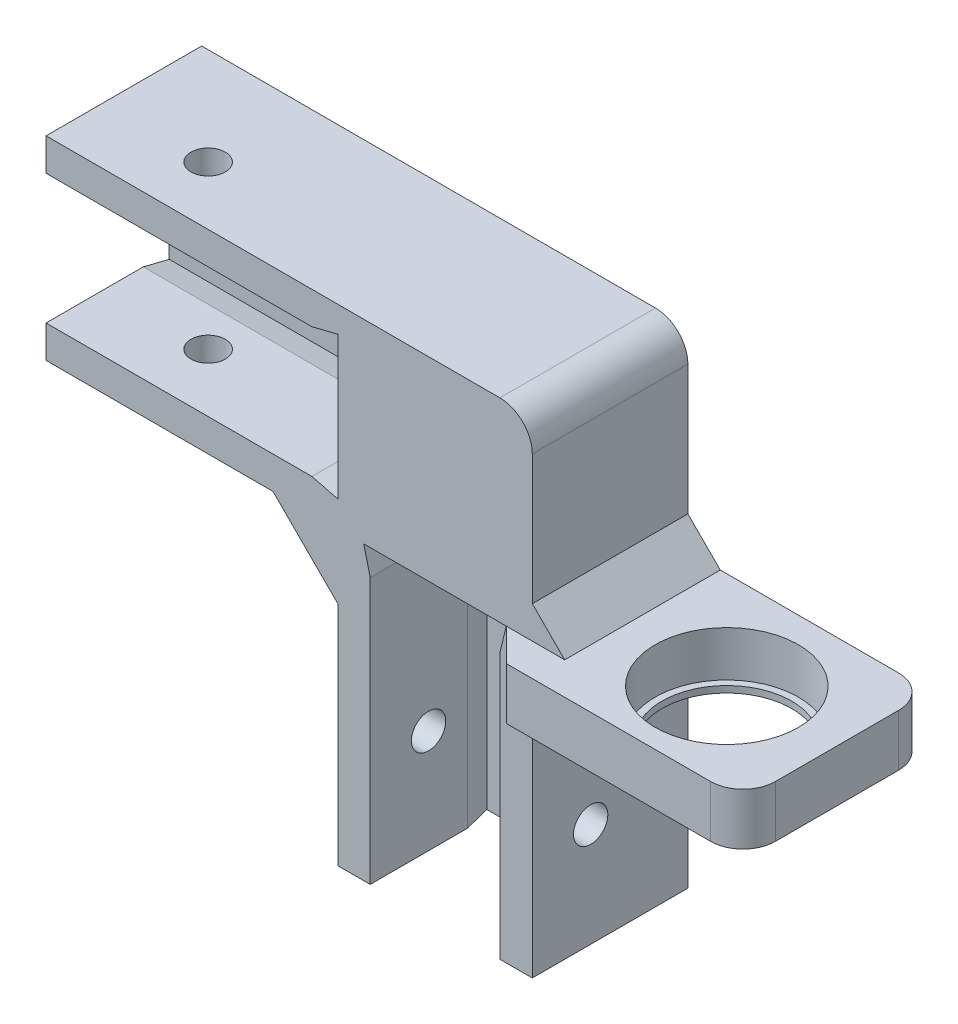
SolidWorks part; units mm, degrees
ref_plane "Front Plane" through (0, 0, 0) normal (0, 0, 1) x (1, 0, 0)
ref_plane "Top Plane" through (0, 0, 0) normal (0, 1, 0) x (1, 0, 0)
ref_plane "Right Plane" through (0, 0, 0) normal (1, 0, 0) x (0, 0, -1)
sketch "Sketch1" plane through (0, 0, 0) normal (0, 0, 1) x (1, 0, 0)
  line L1 (0, 0) -> (75, 0)
  line L2 (0, 0) -> (0, 75)
  line L3 (0, 75) -> (75, 75)
  line L4 (75, 0) -> (75, 75)
  dimension "D1" = 75
  dimension "D2" = 75
extrude "Boss-Extrude1" add sketch "Sketch1" along normal blind 24
sketch "Sketch2" plane through (0, 0, 0) normal (0, -1, 0) x (1, 0, 0)
  line L1 (25, 24) -> (5, 24)
  line L2 (25, 24) -> (25, 5)
  line L3 (25, 5) -> (5, 5)
  line L4 (5, 24) -> (5, 5)
  line L6 (0, 0) -> (75, 0) construction
  line L7 (0, 24) -> (75, 24) construction
  line L8 (0, 24) -> (0, 0) construction
  dimension "D1" = 5
  dimension "D2" = 5
  dimension "D3" = 20
extrude "Cut-Extrude1" cut sketch "Sketch2" against normal blind 45
sketch "Sketch3" plane through (75, 0, 0) normal (1, 0, 0) x (0, 0, -1)
  line L1 (-24, 50) -> (-5, 50)
  line L2 (-24, 50) -> (-24, 70)
  line L3 (-24, 70) -> (-5, 70)
  line L4 (-5, 50) -> (-5, 70)
  line L5 (-24, 75) -> (0, 75) construction
  line L6 (-24, 0) -> (-24, 75) construction
  line L9 (0, 0) -> (0, 75) construction
  dimension "D1" = 5
  dimension "D2" = 20
  dimension "D3" = 5
extrude "Cut-Extrude2" cut sketch "Sketch3" against normal blind 45
sketch "Sketch4" plane through (0, 0, 24) normal (0, 0, 1) x (1, 0, 0)
  line L0 (30, 50) -> (75, 50) construction
  line L1 (75, 0) -> (30, 0)
  line L2 (75, 0) -> (75, 45)
  line L3 (75, 45) -> (30, 45)
  line L4 (30, 0) -> (30, 45)
  line L5 (25, 45) -> (25, 0) construction
  dimension "D1" = 5
  dimension "D2" = 5
extrude "Cut-Extrude3" cut sketch "Sketch4" against normal through all both and the other way through all
fillet "Fillet1" radius 5 1 edges at (0, 75, 12)
chamfer "Chamfer1" distance 10 angle 45 1 edges at (30, 45, 12)
sketch "Sketch5" plane through (0, 0, 0) normal (-1, 0, 0) x (0, 0, 1)
  line L1 (29, 45) -> (0, 45)
  line L2 (29, 45) -> (29, 37)
  line L3 (29, 37) -> (0, 37)
  line L4 (0, 45) -> (0, 37)
  line L5 (5, 45) -> (24, 45) construction
  line L6 (0, 70) -> (0, 0) construction
  dimension "D1" = 8
  dimension "D2" = 29
extrude "Boss-Extrude2" add sketch "Sketch5" along normal blind 37.5
sketch "Sketch6" plane through (0, 45, 0) normal (0, 1, 0) x (1, 0, 0)
  circle A0 centre (-21, -15) radius 11.05
  dimension "D1" = 22.1
extrude "Cut-Extrude4" cut sketch "Sketch6" against normal blind 7
fillet "Fillet2" radius 5 2 edges at (-37.5, 41, 29) (-37.5, 41, 0)
chamfer "Chamfer3" distance 5 angle 45 2 edges at (0, 45, 12) (0, 37, 12)
sketch "Sketch7" plane through (0, 45, 0) normal (0, -1, 0) x (1, 0, 0)
  line L0 (75, 0) -> (75, 24) construction
  line L1 (40, 24) -> (75, 24) construction
  circle A0 centre (59, 15) radius 2.65
  dimension "D1" = 5.3
  dimension "D2" = 16
  dimension "D3" = 9
extrude "Cut-Extrude5" cut sketch "Sketch7" against normal through all both and the other way through all
sketch "Sketch8" plane through (30, 0, 0) normal (1, 0, 0) x (0, 0, -1)
  line L0 (0, 0) -> (-24, 0) construction
  line L1 (-24, 0) -> (-24, 35) construction
  circle A0 centre (-15, 16) radius 2.65
  dimension "D1" = 5.3
  dimension "D2" = 16
  dimension "D3" = 9
extrude "Cut-Extrude6" cut sketch "Sketch8" against normal through all both and the other way through all
sketch "Sketch9" plane through (0, 0, 5) normal (0, 0, 1) x (1, 0, 0)
  line L0 (5, 0) -> (25, 0) construction
  line L1 (25, 45) -> (25, 0) construction
  circle A0 centre (15, 22.5) radius 2.65
  dimension "D1" = 5.3
  dimension "D2" = 22.5
  dimension "D3" = 10
extrude "Cut-Extrude7" cut sketch "Sketch9" against normal blind 10
sketch "Sketch10" plane through (0, 0, 5) normal (0, 0, 1) x (1, 0, 0)
  line L0 (30, 70) -> (75, 70) construction
  line L1 (75, 50) -> (75, 70) construction
  circle A0 centre (52.5, 60) radius 2.65
  dimension "D1" = 5.3
  dimension "D2" = 10
  dimension "D3" = 22.5
extrude "Cut-Extrude8" cut sketch "Sketch10" against normal blind 10
sketch "Sketch11" plane through (0, 0, 24) normal (0, 0, 1) x (1, 0, 0)
  line L0 (34, 70) -> (30, 71)
  line L1 (30, 70) -> (75, 70) construction
  line L2 (30, 71) -> (30, 70)
  line L3 (30, 70) -> (34, 70)
  line L4 (30, 50) -> (34, 50)
  line L5 (30, 50) -> (75, 50) construction
  line L6 (34, 50) -> (30, 49)
  line L7 (30, 49) -> (30, 50)
  line L10 (26, 45) -> (25, 41)
  line L14 (25, 45) -> (25, 0) construction
  line L16 (5, 45) -> (4, 45)
  line L17 (-5, 45) -> (0, 45) construction
  line L18 (4, 45) -> (5, 41)
  line L20 (5, 41) -> (5, 45)
  line L21 (25, 45) -> (26, 45)
  line L22 (25, 41) -> (25, 45)
  dimension "D1" = 4
  dimension "D2" = 1
  dimension "D3" = 1
  dimension "D4" = 4
  dimension "D5" = 1
  dimension "D6" = 1
  dimension "D7" = 4
  dimension "D8" = 4
extrude "Cut-Extrude12" cut sketch "Sketch11" against normal up to surface (19 mm away) up to face at (17.65, 22.5, 5)
sketch "Sketch12" plane through (0, 0, 0) normal (0, -1, 0) x (1, 0, 0)
  line L0 (5, 5) -> (4, 5)
  line L1 (4, 5) -> (5, 9)
  line L2 (5, 24) -> (5, 5) construction
  line L3 (5, 9) -> (5, 5)
  line L4 (25, 5) -> (26, 5)
  line L5 (26, 5) -> (25, 9)
  line L6 (25, 5) -> (25, 24) construction
  line L7 (25, 9) -> (25, 5)
  dimension "D1" = 4
  dimension "D2" = 4
  dimension "D3" = 1
  dimension "D4" = 1
extrude "Cut-Extrude13" cut sketch "Sketch12" against normal up to surface (45 mm away) up to face at (15, 45, 14.5)
sketch "Sketch13" plane through (75, 0, 0) normal (1, 0, 0) x (0, 0, -1)
  line L0 (-5, 50) -> (-5, 49)
  line L1 (-5, 49) -> (-9, 50)
  line L2 (-24, 50) -> (-5, 50) construction
  line L3 (-9, 50) -> (-5, 50)
  line L4 (-5, 70) -> (-5, 71)
  line L5 (-5, 71) -> (-9, 70)
  line L6 (-5, 70) -> (-24, 70) construction
  line L7 (-9, 70) -> (-5, 70)
  dimension "D1" = 1
  dimension "D2" = 4
  dimension "D3" = 4
  dimension "D4" = 1
extrude "Cut-Extrude14" cut sketch "Sketch13" against normal up to surface (45 mm away) up to face at (30, 60, 14.5)
sketch "Sketch14" plane through (0, 38, 0) normal (0, 1, 0) x (1, 0, 0)
  circle A0 centre (-21, -15) radius 10
  dimension "D1" = 20
extrude "Cut-Extrude15" cut sketch "Sketch14" against normal blind 10
chamfer "Chamfer5" distance 4 angle 45 1 edges at (0, 41, 24)
chamfer "Chamfer6" distance 1 angle 45 1 edges at (0, 41, 29)
mirror "Mirror1" about plane through (75, 0, 24) normal (-1, 0, 0) of bodies 117 108
delete or keep bodies "Body-Delete/Keep 1" type delete bodies bodies 117
